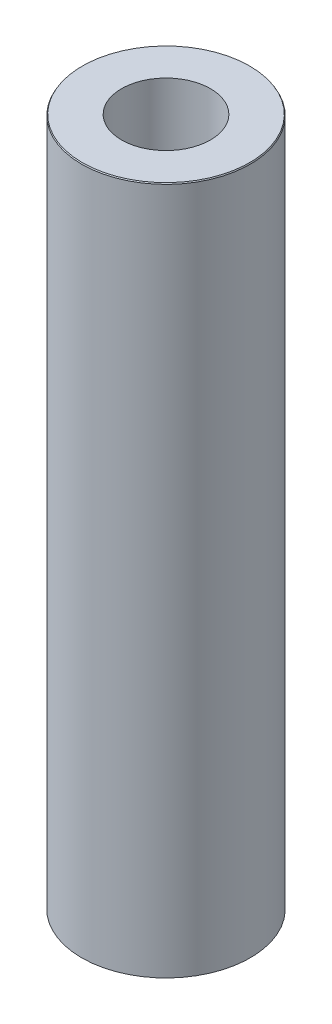
SolidWorks part; units mm, degrees
ref_plane "Front Plane" through (0, 0, 0) normal (0, 0, 1) x (1, 0, 0)
ref_plane "Top Plane" through (0, 0, 0) normal (0, 1, 0) x (1, 0, 0)
ref_plane "Right Plane" through (0, 0, 0) normal (1, 0, 0) x (0, 0, -1)
sketch "Sketch1" plane through (0, 0, 0) normal (0, 1, 0) x (1, 0, 0)
  circle A0 centre (0, 0) radius 40
  dimension "SHAFT_OD" = 80
extrude "Boss-Extrude1" add sketch "Sketch1" along normal blind 326.8476
sketch "Sketch2" plane through (0, 0, 0) normal (0, 1, 0) x (1, 0, 0)
  circle A0 centre (0, 0) radius 21.0945
  dimension "BORE_D" = 42.1891
extrude "Cut-Extrude1" cut sketch "Sketch2" along normal through all
chamfer "Chamfer1" distance 0.5169 angle 30 2 edges at (0, 326.8476, 40) (0, 0, 40) first distance on face at (0, 326.8476, 40) first distance on face at (0, 0, 21.0945)
